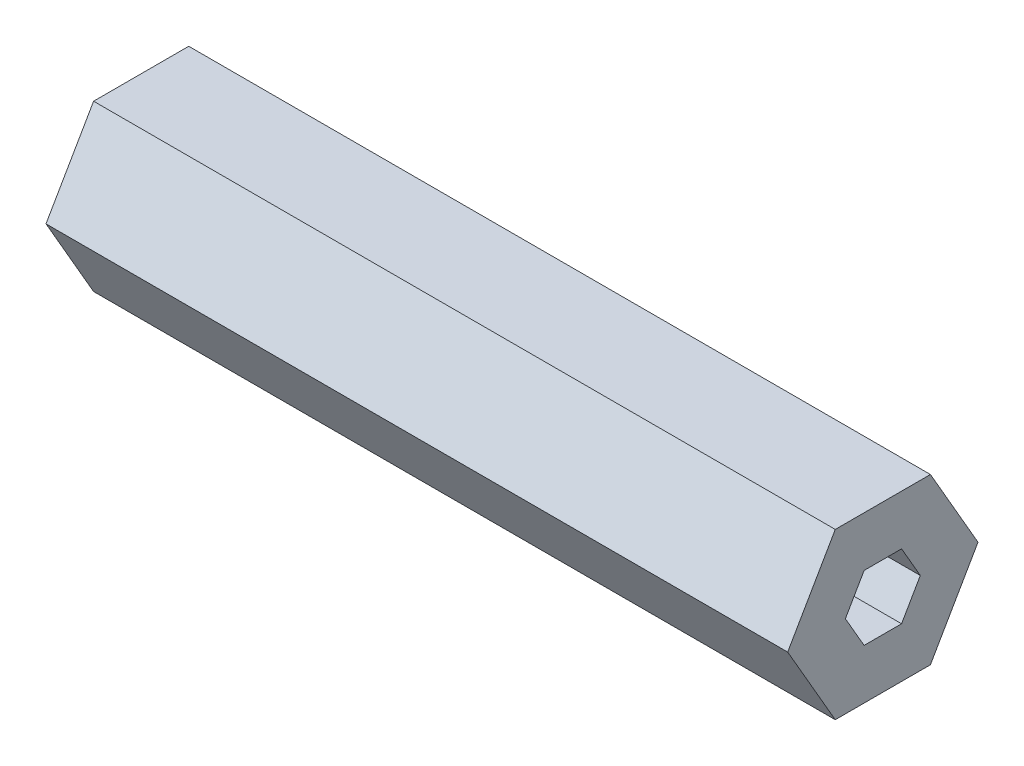
SolidWorks part; units mm, degrees
material "6061-T6 (SS)"
ref_plane "Front" through (0, 0, 0) normal (0, 0, 1) x (1, 0, 0)
ref_plane "Top" through (0, 0, 0) normal (0, 1, 0) x (1, 0, 0)
ref_plane "Right" through (0, 0, 0) normal (1, 0, 0) x (0, 0, -1)
sketch "Sketch1" plane through (0, 0, 0) normal (1, 0, 0) x (0, 0, -1)
  line L1 (7.3323, 0) -> (3.6662, 6.35)
  line L2 (3.6662, 6.35) -> (-3.6662, 6.35)
  line L3 (-3.6662, 6.35) -> (-7.3323, 0)
  line L4 (-7.3323, 0) -> (-3.6662, -6.35)
  line L5 (-3.6662, -6.35) -> (3.6662, -6.35)
  line L6 (3.6662, -6.35) -> (7.3323, 0)
  line L7 (2.8868, 0) -> (1.4434, 2.5)
  line L8 (1.4434, 2.5) -> (-1.4434, 2.5)
  line L9 (-1.4434, 2.5) -> (-2.8868, 0)
  line L10 (-2.8868, 0) -> (-1.4434, -2.5)
  line L11 (-1.4434, -2.5) -> (1.4434, -2.5)
  line L12 (1.4434, -2.5) -> (2.8868, 0)
  circle A0 centre (0, 0) radius 6.35 construction
  circle A1 centre (0, 0) radius 2.5 construction
  dimension "D1" = 12.7
  dimension "D2" = 5
extrude "Boss-Extrude1" add sketch "Sketch1" along normal blind 57.15
ref_axis "Axis1" through (-83.0296, 0, 0) along (1, 0, 0)
